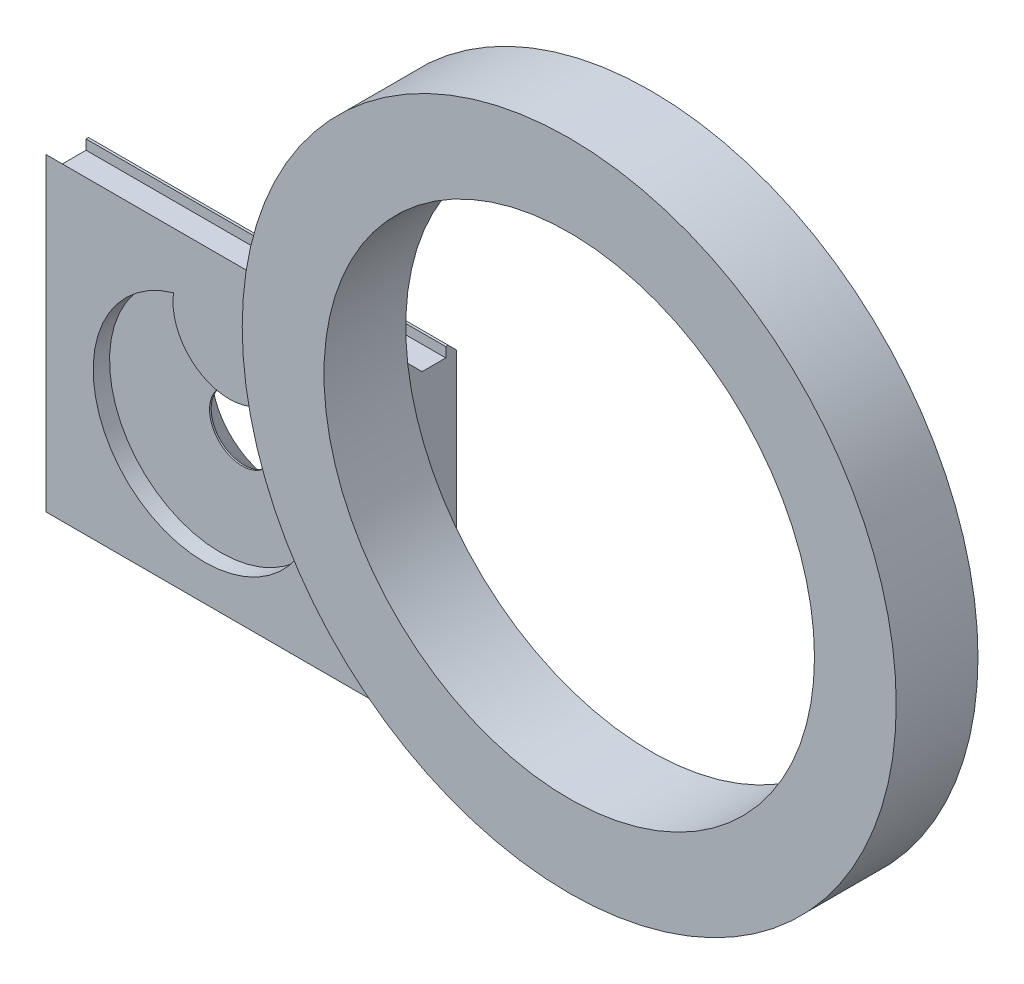
SolidWorks part; units mm, degrees
material "PLA"
ref_plane "Front Plane" through (0, 0, 0) normal (0, 0, 1) x (1, 0, 0)
ref_plane "Top Plane" through (0, 0, 0) normal (0, 1, 0) x (1, 0, 0)
ref_plane "Right Plane" through (0, 0, 0) normal (1, 0, 0) x (0, 0, -1)
sketch "Sketch2" plane through (0, 0, 0) normal (1, 0, 0) x (0, 0, -1)
  line L0 (2, 17.5) -> (4.9, 17.5)
  line L1 (4.9, 17.5) -> (4.9, 18.7)
  line L2 (4.9, 18.7) -> (6.2, 18.7)
  line L3 (6.2, 18.7) -> (6.2, -15.6525)
  line L4 (3, -17.5) -> (0, -17.5) construction
  line L5 (0, -17.5) -> (0, 17.5)
  line L8 (2, 17.5) -> (0, 19.5)
  line L9 (0, 19.5) -> (0, 17.5)
  line L12 (6.2, -15.6525) -> (3, -17.5)
  line L13 (3, -17.5) -> (3, -18.366)
  line L14 (3, -18.366) -> (1.5, -17.5)
  line L15 (1.5, -17.5) -> (0, -18.366)
  line L16 (0, -18.366) -> (0, -17.5)
  point P8 (0, 0)
  dimension "D1" = 35
  dimension "D2" = 6.2
  dimension "D3" = 1.3
  dimension "D4" = 3
  dimension "D5" = 60
  dimension "D6" = 1.2
  dimension "D7" = 37
  dimension "D8" = 45
  dimension "D9" = 30
extrude "Boss-Extrude1" add sketch "Sketch2" along normal mid plane 44 contours L0 L1 L2 L3 L12 L13 L14 L15 L16 L5 L9 L8
sketch "Sketch4" plane through (0, 0, 0) normal (0, 0, 1) x (1, 0, 0)
  circle A0 centre (0, 0.5) radius 4
  dimension "D1" = 8
  dimension "D2" = 0.5
extrude "Cut-Extrude1" cut sketch "Sketch4" against normal through all both and the other way through all
chamfer "Chamfer1" distance 1 angle 45 1 edges at (0, 18.7, -6.2)
chamfer "Chamfer2" distance 4 angle 45 1 edges at (4, 0.5, -6.2)
hole_wizard "CSK for M3 Countersunk Flat Head Screw1" positions "Sketch5" profile "Sketch7" countersink size "M3" standard "ISO"
sketch "Sketch5" plane through (0, 0, -6.2) normal (0, 0, -1) x (-1, 0, 0)
  line L0 (10.5, 0) -> (0, 0)
  line L1 (0, 0) -> (-10.5, 0)
  point P0 (-10.5, 12.5)
  point P2 (10.5, 12.5)
  point P4 (10.5, 0)
  point P6 (-10.5, 0)
  dimension "D1" = 12.5
  dimension "D2" = 21
sketch "Sketch7" plane through (10.5, 12.5, -6.2) normal (1, 0, 0) x (0, 1, 0)
  line L0 (0, 0) -> (0, 3.03)
  line L1 (0, 3.03) -> (0.05, 3)
  line L2 (0.05, 3) -> (0.05, 3.1)
  line L3 (0.05, 3.1) -> (3.15, 0)
  line L5 (3.15, 0) -> (0, 0)
  line L6 (-0.05, 3.1) -> (-3.15, 0) construction
  line L10 (0, 3.03) -> (-0.05, 3) construction
  line L11 (0, -6.35) -> (0, 107.95) construction
  dimension "Hole Dia." = 0.1
  dimension "Hole Depth" = 3
  dimension "Near C'Sink Dia." = 6.3
  dimension "Near C'Sink Angle" = 90
  dimension "Drill Angle" = 118
fillet "Fillet1" radius 0.2 1 edges at (0, -18.366, -3)
sketch "Sketch3" plane through (0, 0, 0) normal (0, 0, 1) x (1, 0, 0)
  arc A0 (6.8755, 9.2942) -> (-6.4032, 12.6518) centre (0.4176, 11.6906) cw
  arc A1 (-6.4032, 12.6518) -> (6.8755, 9.2942) centre (-2.6409, -0.4053) ccw
extrude "Cut-Extrude2" cut sketch "Sketch3" against normal blind 2 contours A1 A0
sketch "Sketch8" [suppressed] plane through (0, 0, 0) normal (0, 0, 1) x (1, 0, 0)
  circle A2 centre (0, -1.0909) radius 12.1052
extrude "Cut-Extrude3" [suppressed] cut sketch "Sketch8" against normal blind 2
sketch "Sketch9" plane through (0, 0, 0) normal (0, 0, 1) x (1, 0, 0)
  line L0 (22, 19.5) -> (22, -18.366) construction
  line L1 (22, 18.7) -> (-22, 18.7) construction
  circle A0 centre (52, 23.247) radius 40
  circle A1 centre (52, 23.247) radius 30
  point P5 (22, 0.567)
  point P8 (0, 18.7)
  dimension "D3" = 10
  dimension "D4" = 80
  dimension "D1" = 22.68
  dimension "D2" = 52
extrude "Boss-Extrude2" add sketch "Sketch9" along normal blind 10 separate body
other "Freeze***"
